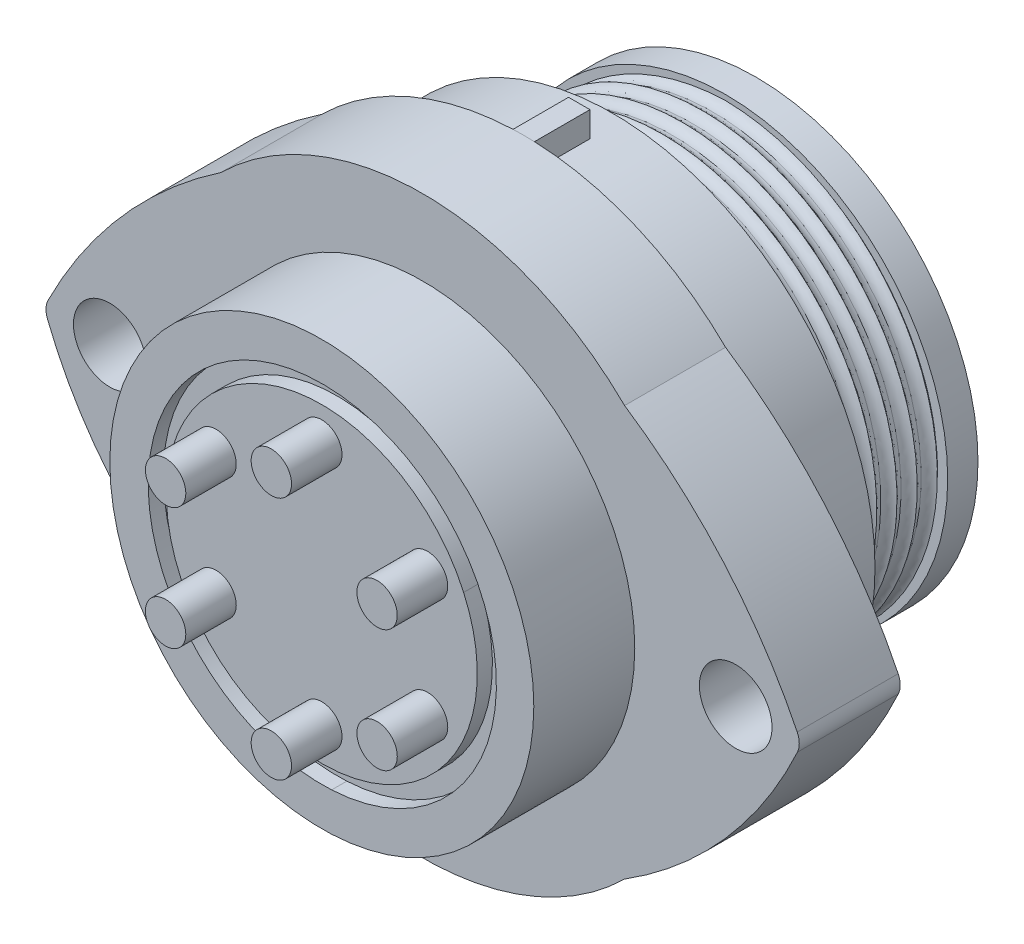
SolidWorks part; units mm, degrees
ref_plane "Front Plane" through (0, 0, 0) normal (0, 0, 1) x (1, 0, 0)
ref_plane "Top Plane" through (0, 0, 0) normal (0, 1, 0) x (1, 0, 0)
ref_plane "Right Plane" through (0, 0, 0) normal (1, 0, 0) x (0, 0, -1)
sketch "Sketch1" plane through (0, 0, 0) normal (0, 0, 1) x (1, 0, 0)
  circle A0 centre (0, 0) radius 10.5
  dimension "D1" = 21
extrude "Boss-Extrude1" add sketch "Sketch1" along normal blind 5
sketch "Sketch2" plane through (0, 0, 0) normal (0, 0, 1) x (1, 0, 0)
  arc A12 (9.9974, 10.1546) -> (-9.9974, 10.1546) centre (0, 0) ccw
  arc A13 (9.9974, 10.1546) -> (18.75, 0) centre (-3.668, -10.4735) cw
  arc A14 (18.75, 0) -> (9.9974, -10.1546) centre (-2.0445, 9.0742) cw
  arc A15 (-9.9974, 10.1546) -> (-18.75, 0) centre (4.3482, -11.0599) ccw
  arc A16 (-9.9974, -10.1546) -> (-18.75, 0) centre (-0.8564, 6.5738) cw
  arc A17 (-9.9974, -10.1546) -> (9.9974, -10.1546) centre (0, 0) ccw
  dimension "D1" = 28.5
  dimension "D2" = 18.75
  dimension "D3" = 18.75
extrude "Boss-Extrude2" add sketch "Sketch2" against normal blind 5
sketch "Sketch3" plane through (0, 0, -5) normal (0, 0, -1) x (-1, 0, 0)
  circle A2 centre (-15.5, 0) radius 1.8
  circle A3 centre (15.5, 0) radius 1.8
  dimension "D1" = 3.6
  dimension "D2" = 3.6
extrude "Cut-Extrude1" cut sketch "Sketch3" against normal blind 5
fillet "Fillet1" radius 1 2 edges at (-18.75, 0, -2.5) (18.75, 0, -2.5)
sketch "Sketch6" plane through (0, 0, 5) normal (0, 0, 1) x (1, 0, 0)
  circle A0 centre (0, 6.0476) radius 1
extrude "Boss-Extrude6" add sketch "Sketch6" along normal blind 2.5
pattern_circular "CirPattern2" count 6 over 360 about axis through (0, 0, 0) along (0, 0, 1) of "Boss-Extrude6"
sketch "Sketch7" plane through (0, 0, -5) normal (0, 0, -1) x (-1, 0, 0)
  circle A0 centre (0, 0) radius 13
  dimension "D1" = 26
extrude "Boss-Extrude7" add sketch "Sketch7" along normal blind 4.4
sketch "Sketch8" plane through (0, 0, -9.4) normal (0, 0, -1) x (-1, 0, 0)
  circle A0 centre (0, 0) radius 11
  dimension "D1" = 22
extrude "Boss-Extrude8" add sketch "Sketch8" along normal blind 5.6
sketch "Sketch12" plane through (0, 0, -15) normal (0, 0, -1) x (-1, 0, 0)
  circle A0 centre (0, 0) radius 11 construction
  circle A1 centre (0, 0) radius 11
curve "Helix/Spiral1" pitch 1 height 5.6 turns 5.6
sketch "Sketch13" plane through (0, 0, 0) normal (1, 0, 0) x (0, 0, -1)
  circle A0 centre (15, -11) radius 0.5649
sweep "Cut-Sweep1" cut profiles "Sketch13" path "Helix/Spiral1" align with end faces yes
sketch "Sketch14" plane through (0, 0, -15) normal (0, 0, -1) x (-1, 0, 0)
  circle A0 centre (0, 0) radius 11
  dimension "D1" = 22
extrude "Boss-Extrude9" add sketch "Sketch14" along normal blind 1.5
sketch "Sketch15" plane through (0, 0, -16.5) normal (0, 0, -1) x (-1, 0, 0)
  circle A0 centre (0, 0) radius 9.5
  dimension "D1" = 19
extrude "Cut-Extrude2" cut sketch "Sketch15" against normal blind 3.5
sketch "Sketch16" plane through (0, 0, -13) normal (0, 0, -1) x (-1, 0, 0)
  circle A0 centre (0, 0) radius 6.15
  dimension "D1" = 12.3
extrude "Boss-Extrude10" add sketch "Sketch16" along normal blind 5
sketch "Sketch17" plane through (0, 0, -18) normal (0, 0, -1) x (-1, 0, 0)
  circle A1 centre (0, 3.43) radius 1
extrude "Cut-Extrude3" cut sketch "Sketch17" against normal blind 3
pattern_circular "CirPattern3" count 6 over 360 about axis through (0, 0, 0) along (0, 0, 1) of "Cut-Extrude3"
sketch "Sketch18" plane through (0, 0, -5) normal (0, 0, -1) x (-1, 0, 0)
  line L1 (0.5298, 12.9701) -> (-0.5298, 12.9701)
  line L2 (0.5298, 12.9701) -> (0.5298, 14.2401)
  line L3 (0.5298, 14.2401) -> (-0.5298, 14.2401)
  line L4 (-0.5298, 12.9701) -> (-0.5298, 14.2401)
  line L5 (0.5298, 12.9701) -> (-0.5298, 14.2401) construction
  line L6 (0.5298, 14.2401) -> (-0.5298, 12.9701) construction
  arc A0 (9.9974, 10.1546) -> (-9.9974, 10.1546) centre (0, 0) ccw construction
  point P0 (0, 13.6051)
  dimension "D1" = 1.27
extrude "Boss-Extrude11" add sketch "Sketch18" along normal blind 2.75
sketch "Sketch24" plane through (0, 0, 5) normal (0, 0, 1) x (1, 0, 0)
  arc A0 (-0.7464, 8.5675) -> (-8.5959, -0.267) centre (0, 0) ccw
  arc A1 (-8.5959, -0.267) -> (0.4877, -8.5844) centre (-0.0001, 0.0017) ccw
  arc A2 (0.4877, -8.5844) -> (8.6446, 0.237) centre (0.0478, 0.0043) ccw
  arc A3 (8.6446, 0.237) -> (-0.7464, 8.5675) centre (0.0478, 0.0043) ccw
  arc A4 (-7.6963, -0.239) -> (-6.9983, -3.2115) centre (0, 0) ccw
  arc A5 (-6.9983, -3.2115) -> (6.2082, -4.555) centre (0, 0) ccw
  arc A6 (6.2082, -4.555) -> (7.025, 3.1542) centre (0.0004, 0.0006) ccw
  arc A7 (7.025, 3.1542) -> (-7.6963, -0.239) centre (-0.0001, 0.0017) ccw
extrude "Cut-Extrude6" cut sketch "Sketch24" against normal blind 0.75
